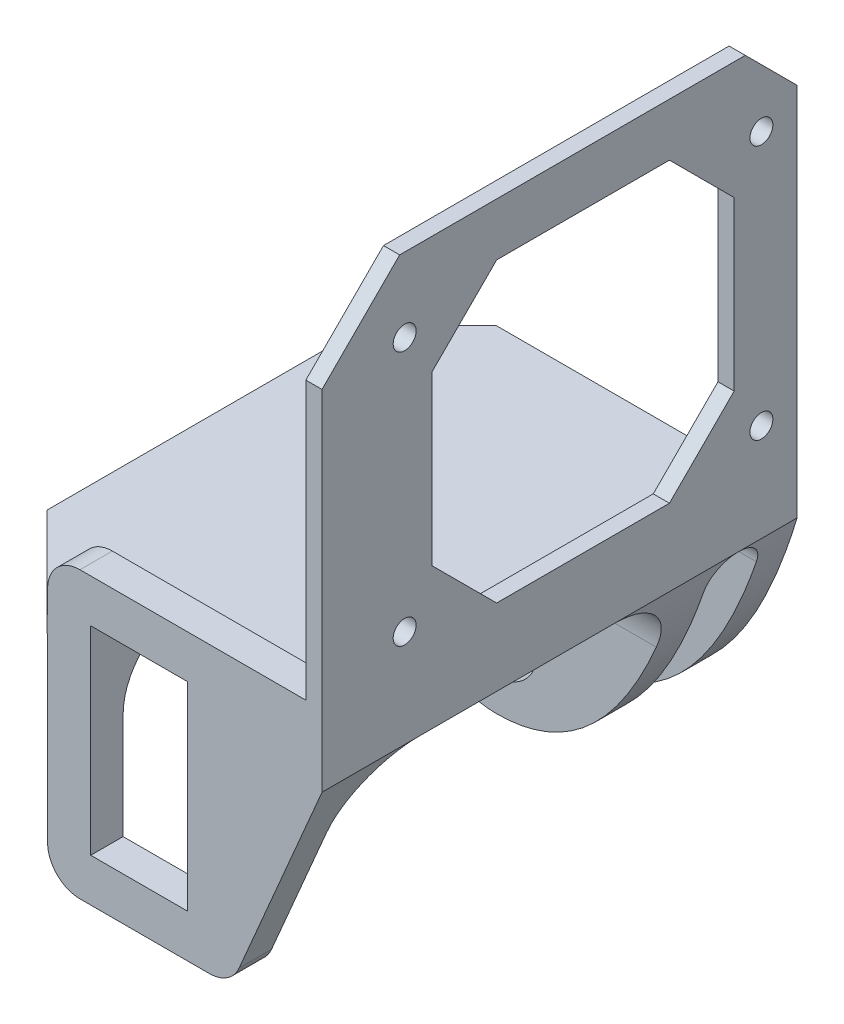
SolidWorks part; units mm, degrees
material "ABS PC"
ref_plane "Front Plane" through (0, 0, 0) normal (0, 0, 1) x (1, 0, 0)
ref_plane "Top Plane" through (0, 0, 0) normal (0, 1, 0) x (1, 0, 0)
ref_plane "Right Plane" through (0, 0, 0) normal (1, 0, 0) x (0, 0, -1)
sketch "Sketch1" plane through (0, 0, 0) normal (0, 1, 0) x (1, 0, 0)
  line L0 (0, 46.609) -> (71.755, 46.609) construction
  line L1 (0, 0) -> (71.755, 0)
  line L2 (0, 0) -> (0, 93.218)
  line L3 (0, 93.218) -> (71.755, 93.218)
  line L4 (71.755, 0) -> (71.755, 93.218)
  line L5 (35.8775, 93.218) -> (35.8775, 0) construction
  dimension "D1" = 71.755
  dimension "D2" = 93.218
extrude "Boss-Extrude1" add sketch "Sketch1" along normal blind 3.175
ref_plane "Plane2" through (0, 0, -46.609) normal (0, 0, -1) x (-1, 0, 0)
ref_plane "Plane1" through (35.8775, 0, 0) normal (1, 0, 0) x (0, 0, -1)
sketch "Sketch3" plane through (0, 3.175, 0) normal (0, 1, 0) x (1, 0, 0)
  line L0 (71.755, 0) -> (68.58, 0)
  line L1 (0, 0) -> (71.755, 0) construction
  line L2 (68.58, 0) -> (68.58, 93.218)
  line L3 (71.755, 93.218) -> (0, 93.218) construction
  line L4 (68.58, 93.218) -> (71.755, 93.218)
  line L5 (71.755, 93.218) -> (71.755, 0)
  dimension "D1" = 3.175
extrude "Boss-Extrude4" add sketch "Sketch3" along normal blind 80.518
sketch "Sketch8" plane through (0, 0, -46.609) normal (0, 0, 1) x (1, 0, 0)
  line L1 (0, 0) -> (71.755, 0) construction
  line L5 (35.8775, -46.0311) -> (35.8775, 46.0311) construction
  line L7 (35.8775, 0) -> (35.8775, -33.4) construction
  line L8 (45.3775, 0) -> (45.3775, -33.4)
  line L9 (45.3775, -33.4) -> (26.3775, -33.4)
  line L10 (26.3775, -33.4) -> (26.3775, 0)
  line L11 (45.3775, 0) -> (45.3775, 5.6)
  line L12 (45.3775, 5.6) -> (26.3775, 5.6)
  line L13 (26.3775, 5.6) -> (26.3775, 0)
  line L14 (17.9108, 14.0667) -> (17.9108, 0)
  line L15 (17.9108, -41.8667) -> (17.9108, 0)
  line L16 (53.8442, -41.8667) -> (17.9108, -41.8667)
  line L17 (53.8442, 0) -> (53.8442, -41.8667) construction
  line L18 (53.8442, 0) -> (53.8442, 14.0667) construction
  line L19 (53.8442, 14.0667) -> (17.9108, 14.0667)
  line L20 (53.8442, 14.0667) -> (71.755, 14.0667)
  line L21 (71.755, 83.693) -> (71.755, 0) construction
  line L22 (71.755, 14.0667) -> (71.755, 0)
  line L23 (71.755, 0) -> (53.8442, -41.8667)
  dimension "D3" = 8.4667
  dimension "D4" = 33.4
  dimension "D1" = 39
  dimension "D2" = 19
extrude "Boss-Extrude10" add sketch "Sketch8" against normal blind 6.35 from surface contours L22 L23 L16 L15 L14 L19 L20 L12 L13 L10 L9 L8 L11 starting at face at (46.7783, 28.956, 0)
sketch "Sketch16" plane through (0, 0, 0) normal (0, 0, -1) x (-1, 0, 0)
  line L4 (-26.3775, 5.6) -> (-26.3775, -33.4)
  line L5 (-26.3775, -33.4) -> (-45.3775, -33.4)
  line L6 (-45.3775, -33.4) -> (-45.3775, 5.6)
  line L7 (-45.3775, 5.6) -> (-26.3775, 5.6)
extrude "Cut-Extrude5" cut sketch "Sketch16" along normal blind 6.35
sketch "Sketch11" plane through (71.755, 0, 0) normal (1, 0, 0) x (0, 0, -1)
  line L7 (0, 0) -> (6.35, 0)
  line L8 (0, 0) -> (6.35, 0)
  line L9 (93.218, 83.693) -> (0, 83.693)
  line L11 (0, 83.693) -> (0, 0)
  line L16 (93.218, 0) -> (93.218, 83.693)
  line L17 (6.35, 0) -> (93.218, 0)
  line L18 (93.218, 83.693) -> (0, 83.693)
  line L20 (0, 83.693) -> (0, 0)
  line L25 (93.218, 0) -> (93.218, 83.693)
  line L28 (6.35, 0) -> (93.218, 0)
  arc A16 (86.218, 21.425) -> (86.218, 16.925) centre (86.218, 19.175) ccw construction
  arc A17 (86.218, 16.925) -> (86.218, 21.425) centre (86.218, 19.175) ccw construction
  arc A18 (16.218, 21.425) -> (16.218, 16.925) centre (16.218, 19.175) ccw construction
  arc A19 (16.218, 16.925) -> (16.218, 21.425) centre (16.218, 19.175) ccw construction
  arc A20 (16.218, 71.425) -> (16.218, 66.925) centre (16.218, 69.175) ccw construction
  arc A21 (16.218, 66.925) -> (16.218, 71.425) centre (16.218, 69.175) ccw construction
  arc A22 (86.218, 71.425) -> (86.218, 66.925) centre (86.218, 69.175) ccw construction
  arc A23 (86.218, 66.925) -> (86.218, 71.425) centre (86.218, 69.175) ccw construction
  arc A24 (86.218, 21.425) -> (86.218, 16.925) centre (86.218, 19.175) ccw
  arc A25 (86.218, 16.925) -> (86.218, 21.425) centre (86.218, 19.175) ccw
  arc A26 (16.218, 21.425) -> (16.218, 16.925) centre (16.218, 19.175) ccw
  arc A27 (16.218, 16.925) -> (16.218, 21.425) centre (16.218, 19.175) ccw
  arc A28 (16.218, 71.425) -> (16.218, 66.925) centre (16.218, 69.175) ccw
  arc A29 (16.218, 66.925) -> (16.218, 71.425) centre (16.218, 69.175) ccw
  arc A30 (86.218, 71.425) -> (86.218, 66.925) centre (86.218, 69.175) ccw
  arc A31 (86.218, 66.925) -> (86.218, 71.425) centre (86.218, 69.175) ccw
  dimension "D1" = 0
extrude "Cut-Extrude2" cut sketch "Sketch11" against normal up to next contours A28 A29 | A30 A31 | A24 A25 | A26 A27
sketch "Sketch9" plane through (71.755, 0, 0) normal (1, 0, 0) x (0, 0, -1)
  line L0 (6.35, 0) -> (6.35, 83.693) construction
  line L2 (21.5635, 15.0285) -> (80.8725, 15.0285)
  line L3 (21.5635, 15.0285) -> (21.5635, 73.3215)
  line L4 (21.5635, 73.3215) -> (80.8725, 73.3215)
  line L5 (80.8725, 15.0285) -> (80.8725, 73.3215)
  line L6 (21.5635, 15.0285) -> (80.8725, 73.3215) construction
  line L7 (21.5635, 73.3215) -> (80.8725, 15.0285) construction
  line L8 (0, 83.693) -> (93.218, 83.693) construction
  line L9 (16.218, 69.175) -> (86.218, 19.175) construction
  point P4 (51.218, 44.175)
  point P9 (51.218, 44.175)
  dimension "D1" = 59.309
  dimension "D5" = 58.293
extrude "Cut-Extrude1" cut sketch "Sketch9" against normal up to next contours L3 L2 L5 L4
chamfer "Chamfer1" distance 12.7 angle 45 4 edges at (70.1675, 15.0285, -21.5635) (70.1675, 15.0285, -80.8725) (70.1675, 73.3215, -80.8725) (70.1675, 73.3215, -21.5635)
fillet "Fillet3" radius 12.7 1 edges at (0, 1.5875, -93.218) profile chamfer
sketch "Sketch10" plane through (0, 0, -93.218) normal (0, 0, 1) x (1, 0, 0)
  line L0 (35.8775, -25.4) -> (35.8775, 0) construction
  line L7 (35.8775, -25.4) -> (35.8775, -39.6875) construction
  line L8 (71.755, 0) -> (12.7, 0)
  circle A0 centre (35.8775, -25.4) radius 7.9375
  circle A5 centre (35.8775, -25.4) radius 14.2875 construction
  spline S0 degree 2 poles (35.8775, -39.6875) (16.2478, -39.6875) (12.7, 0) knots 0 0 0 1 1 1
  spline S1 degree 2 poles (35.8775, -39.6875) (59.8112, -39.6875) (71.755, 0) knots 0 0 0 1 1 1
  dimension "D1" = 15.875
  dimension "D2" = 14.2875
  dimension "D3" = 25.4
extrude "Boss-Extrude11" add sketch "Sketch10" along normal blind 6.35 from surface starting at face at (51.0117, 28.956, -93.218)
pattern_linear "LPattern1" count 2 spacing 16.7132 along (0, 0, 1) of "Boss-Extrude11"
fillet "Fillet5" radius 6.35 3 edges at (53.8442, -41.8667, -3.175) (17.9108, 14.0667, -3.175) (17.9108, -41.8667, -3.175)
fillet "Fillet8" radius 5.08 2 edges at (42.2275, 0, -76.5048)
fillet "Fillet9" radius 12.7 3 edges at (22.1442, 0, -6.35) (58.5663, 0, -6.35) (42.2275, 0, -70.1548)
chamfer "Chamfer2" distance 10.16 angle 45 1 edges at (70.1675, 83.693, -93.218)
chamfer "Chamfer3" distance 15.24 angle 45 1 edges at (70.1675, 83.693, 0)
chamfer "Chamfer4" distance 17.78 angle 45 1 edges at (0, 1.5875, 0)
equation "\"D2@Sketch10\"=0.3125+0.25"
